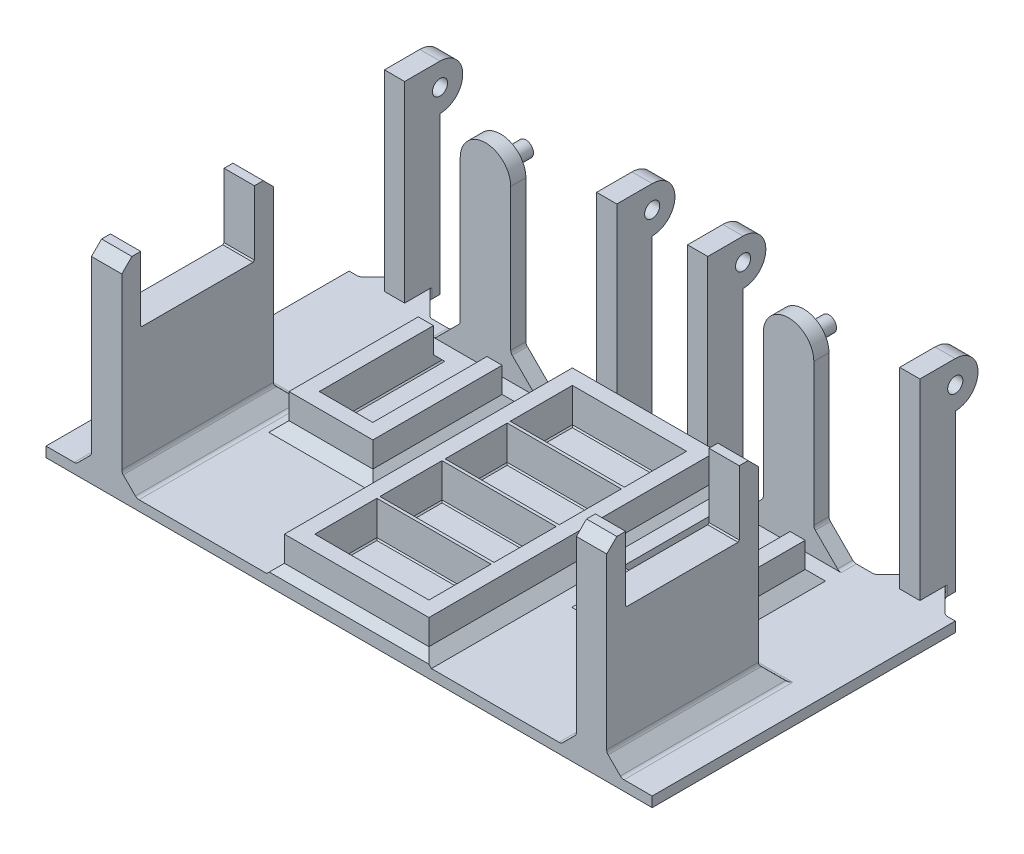
SolidWorks part; units mm, degrees
ref_plane "Front Plane" through (0, 0, 0) normal (0, 0, 1) x (1, 0, 0)
ref_plane "Top Plane" through (0, 0, 0) normal (0, 1, 0) x (1, 0, 0)
ref_plane "Right Plane" through (0, 0, 0) normal (1, 0, 0) x (0, 0, -1)
sketch "Sketch1" plane through (0, 0, 0) normal (0, 1, 0) x (1, 0, 0)
  line L0 (-60, -30) -> (-51, -30)
  line L1 (-60, -30) -> (60, -30)
  line L2 (-60, -30) -> (-60, 30)
  line L3 (-60, 30) -> (60, 30)
  line L4 (60, -30) -> (60, 30)
  line L5 (-60, -30) -> (60, 30) construction
  line L6 (-60, 30) -> (60, -30) construction
  line L7 (-51, -30) -> (-45, -30)
  line L8 (-45, -30) -> (-45, 0)
  line L9 (-45, 0) -> (-51, 0)
  line L10 (-51, 0) -> (-51, -30)
  line L11 (51, -30) -> (51, 0)
  line L12 (51, 0) -> (45, 0)
  line L13 (45, 0) -> (45, -30)
  line L14 (45, -30) -> (51, -30)
  line L15 (-38.3, 22) -> (-38.3, -3.6)
  line L16 (-38.3, -3.6) -> (-21.7, -3.6)
  line L17 (-21.7, -3.6) -> (-21.7, 22)
  line L18 (-21.7, 22) -> (-24.7, 22)
  line L19 (-24.7, 22) -> (-24.7, -0.6)
  line L20 (-24.7, -0.6) -> (-35.3, -0.6)
  line L21 (-35.3, -0.6) -> (-35.3, 22)
  line L22 (-35.3, 22) -> (-38.3, 22)
  line L23 (21.7, 22) -> (21.7, -3.6)
  line L24 (21.7, -3.6) -> (38.3, -3.6)
  line L25 (38.3, -3.6) -> (38.3, 22)
  line L26 (38.3, 22) -> (35.3, 22)
  line L27 (35.3, 22) -> (35.3, -0.6)
  line L28 (35.3, -0.6) -> (24.7, -0.6)
  line L29 (24.7, -0.6) -> (24.7, 22)
  line L30 (24.7, 22) -> (21.7, 22)
  line L31 (-25, 30) -> (-25, 27)
  line L32 (-25, 27) -> (-35, 27)
  line L33 (-35, 27) -> (-35, 30)
  line L34 (-35, 30) -> (-25, 30)
  line L35 (25, 30) -> (25, 27)
  line L36 (25, 27) -> (35, 27)
  line L37 (35, 27) -> (35, 30)
  line L38 (35, 30) -> (25, 30)
  line L39 (-53, 30) -> (-53, 37)
  line L40 (-53, 37) -> (-49, 37)
  line L41 (-49, 37) -> (-49, 30)
  line L42 (-7, 30) -> (-7, 37)
  line L43 (-7, 37) -> (-11, 37)
  line L44 (-11, 37) -> (-11, 30)
  line L45 (-11, 30) -> (-7, 30)
  line L46 (-53, 30) -> (-49, 30)
  line L47 (7, 30) -> (7, 37)
  line L48 (7, 37) -> (11, 37)
  line L49 (11, 37) -> (11, 30)
  line L50 (7, 30) -> (11, 30)
  line L51 (49, 30) -> (49, 37)
  line L52 (49, 37) -> (53, 37)
  line L53 (53, 37) -> (53, 30)
  line L54 (53, 30) -> (49, 30)
  line L55 (0, 0) -> (0, 30) construction
  line L64 (0, 0) -> (-60, 0) construction
  line L65 (-30, 0) -> (-30, 30) construction
  line L66 (0, 0) -> (60, 0) construction
  line L67 (30, 0) -> (30, 30) construction
  line L68 (-11.3, 13.2) -> (11.3, 13.2)
  line L69 (-11.3, -25.5) -> (11.3, -25.5)
  line L70 (-11.3, -25.5) -> (-11.3, 25.5)
  line L71 (-11.3, 25.5) -> (11.3, 25.5)
  line L72 (11.3, -25.5) -> (11.3, 25.5)
  line L73 (-11.3, -25.5) -> (11.3, 25.5) construction
  line L74 (-11.3, 25.5) -> (11.3, -25.5) construction
  line L75 (-14.3, -28.5) -> (14.3, -28.5)
  line L76 (-14.3, -28.5) -> (-14.3, 28.5)
  line L77 (-14.3, 28.5) -> (14.3, 28.5)
  line L78 (14.3, -28.5) -> (14.3, 28.5)
  line L79 (-14.3, -28.5) -> (14.3, 28.5) construction
  line L80 (-14.3, 28.5) -> (14.3, -28.5) construction
  line L81 (11.3, 13.2) -> (11.3, 12.6)
  line L82 (11.3, 12.6) -> (-11.3, 12.6)
  line L83 (-11.3, 12.6) -> (-11.3, 13.2)
  line L84 (-11.3, 0.3) -> (11.3, 0.3)
  line L85 (11.3, 0.3) -> (11.3, -0.3)
  line L86 (11.3, -0.3) -> (-11.3, -0.3)
  line L87 (-11.3, -0.3) -> (-11.3, 0.3)
  line L88 (-11.3, -12.6) -> (11.3, -12.6)
  line L89 (11.3, -12.6) -> (11.3, -13.2)
  line L90 (11.3, -13.2) -> (-11.3, -13.2)
  line L91 (-11.3, -13.2) -> (-11.3, -12.6)
  point P0 (0, 0)
  point P80 (36.8, 22)
  dimension "D1" = 120
  dimension "D2" = 60
  dimension "D3" = 9
  dimension "D4" = 6
  dimension "D5" = 30
  dimension "D6" = 6
  dimension "D7" = 30
  dimension "D8" = 9
  dimension "D9" = 7
  dimension "D10" = 4
  dimension "D11" = 7
  dimension "D12" = 7
  dimension "D13" = 4
  dimension "D14" = 7
  dimension "D15" = 4
  dimension "D16" = 7
  dimension "D17" = 4
  dimension "D18" = 7
  dimension "D19" = 7
  dimension "D20" = 3
  dimension "D21" = 10
  dimension "D22" = 5
  dimension "D23" = 22.6
  dimension "D24" = 10.6
  dimension "D25" = 25.6
  dimension "D26" = 3
  dimension "D27" = 3
  dimension "D28" = 3
  dimension "D29" = 25.6
  dimension "D30" = 3
  dimension "D31" = 25.6
  dimension "D32" = 3
  dimension "D33" = 3
  dimension "D34" = 10.6
  dimension "D35" = 3
  dimension "D36" = 10
  dimension "D37" = 7
  dimension "D38" = 5
  dimension "D39" = 5.3
  dimension "D40" = 5.3
  dimension "D41" = 5
  dimension "D42" = 5
  dimension "D43" = 51
  dimension "D44" = 22.6
  dimension "D45" = 3
  dimension "D46" = 3
  dimension "D47" = 0.6
  dimension "D48" = 12.3
  dimension "D49" = 0.6
  dimension "D50" = 12.3
  dimension "D51" = 12.3
  dimension "D52" = 12.3
  dimension "D53" = 25.6
extrude "Boss-Extrude1" add sketch "Sketch1" along normal blind 9 contours L29 L30 L23 L24 L25 L26 L27 L28 | L22 L15 L16 L17 L18 L19 L20 L21 region at (23.2, 0, -21.6949)
extrude "Boss-Extrude2" add sketch "Sketch1<3>" along normal blind 28 separate body contours L7 L8 L9 L10 | L12 L13 L14 L11
sketch "Sketch1<3>" plane through (0, 0, 0) normal (0, 1, 0) x (1, 0, 0) same geometry as "Sketch1"
extrude "Boss-Extrude3" add sketch "Sketch1<4>" along normal blind 40 separate body contours L40 L41 L46 L39 | L43 L44 L45 L42 | L48 L49 L50 L47 | L52 L53 L54 L51
sketch "Sketch1<4>" plane through (0, 0, 0) normal (0, 1, 0) x (1, 0, 0) same geometry as "Sketch1"
extrude "Boss-Extrude4" add sketch "Sketch1<5>" along normal blind 35.5 separate body contours L36 L37 L3 L35 | L31 L32 L33 L34 region at (30, 0, -28.5)
sketch "Sketch1<5>" plane through (0, 0, 0) normal (0, 1, 0) x (1, 0, 0) same geometry as "Sketch1"
extrude "Boss-Extrude5" add sketch "Sketch1<6>" along normal blind 2 contours L2 L3 L4 L1
sketch "Sketch1<6>" plane through (0, 0, 0) normal (0, 1, 0) x (1, 0, 0) same geometry as "Sketch1"
extrude "Boss-Extrude6" add sketch "Sketch1<8>" along normal blind 9 contours L72 L71 L70 L69 | L76 L77 L78 L75
sketch "Sketch1<8>" plane through (0, 0, 0) normal (0, 1, 0) x (1, 0, 0) same geometry as "Sketch1"
extrude "Boss-Extrude7" add sketch "Sketch1<9>" along normal blind 9 contours L68 L81 L82 L83 | L84 L85 L86 L87 | L88 L89 L90 L91
sketch "Sketch1<9>" plane through (0, 0, 0) normal (0, 1, 0) x (1, 0, 0) same geometry as "Sketch1"
sketch "Sketch2" plane through (0, 28, 0) normal (0, 1, 0) x (1, 0, 0)
  line L0 (-51, 0) -> (-45, 0)
  line L1 (-45, 0) -> (-45, -3.75)
  line L2 (-45, -30) -> (-45, 0) construction
  line L3 (-45, -3.75) -> (-51, -3.75)
  line L4 (-51, 0) -> (-51, -30) construction
  line L5 (-51, -3.75) -> (-51, 0)
  line L6 (-45, -30) -> (-45, -26.25)
  line L7 (-45, -26.25) -> (-51, -26.25)
  line L8 (-51, -26.25) -> (-51, -30)
  line L9 (-51, -30) -> (-45, -30)
  line L10 (45, 0) -> (51, 0)
  line L11 (51, 0) -> (51, -3.75)
  line L12 (51, -30) -> (51, 0) construction
  line L13 (51, -3.75) -> (45, -3.75)
  line L14 (45, 0) -> (45, -30) construction
  line L15 (45, -3.75) -> (45, 0)
  line L16 (45, -26.25) -> (51, -26.25)
  line L17 (51, -26.25) -> (51, -30)
  line L18 (51, -30) -> (45, -30)
  line L19 (45, -30) -> (45, -26.25)
  dimension "D1" = 22.5
  dimension "D2" = 3.75
  dimension "D3" = 22.5
extrude "Boss-Extrude8" add sketch "Sketch2" along normal blind 13
sketch "Sketch3" plane through (0, 0, -27) normal (0, 0, 1) x (1, 0, 0)
  line L0 (25, 35.5) -> (35, 35.5) construction
  line L1 (25, 35.5) -> (25, 2) construction
  line L2 (-25, 35.5) -> (-35, 35.5) construction
  line L3 (-35, 35.5) -> (-35, 2) construction
  line L4 (-35, 35.5) -> (-25, 35.5)
  line L5 (25, 35.5) -> (35, 35.5)
  arc A0 (35, 35.5) -> (25, 35.5) centre (30, 35.5) ccw
  arc A1 (-25, 35.5) -> (-35, 35.5) centre (-30, 35.5) ccw
  circle A2 centre (-30, 35.5) radius 1.5
  circle A3 centre (30, 35.5) radius 1.5
  line M3 (35, 35.5) -> (25, 35.5)
  dimension "D1" = 3
  dimension "D2" = 3
extrude "Boss-Extrude9" add sketch "Sketch3" against normal up to surface (3 mm away) contours A3 A0 M3 | A2 L4 A1 region at (-30, 37.769, -27) region at (30, 37.769, -27) up to face at (-30, 9.875, -30)
extrude "Boss-Extrude11" add sketch "Sketch3<5>" against normal blind 8 contours A3 | A2
sketch "Sketch3<5>" plane through (0, 0, -27) normal (0, 0, 1) x (1, 0, 0) same geometry as "Sketch3"
sketch "Sketch4" plane through (-53, 0, 0) normal (-1, 0, 0) x (0, 0, 1)
  line L2 (-30, 40) -> (-37, 40) construction
  circle A1 centre (-37, 35.5) radius 1.5
  circle A2 centre (-37, 35.5) radius 4.5
  dimension "D1" = 9
  dimension "D2" = 4.5
  dimension "D3" = 3
extrude "Boss-Extrude13" add sketch "Sketch4" against normal up to surface (4 mm away) contours A2 | A1 up to face at (-49, 16.4, -32.8)
extrude "Cut-Extrude2" cut sketch "Sketch4<4>" against normal up to surface (4 mm away) contours A1 up to face at (-49, 18.8333, -34.25)
sketch "Sketch4<4>" plane through (-53, 0, 0) normal (-1, 0, 0) x (0, 0, 1) same geometry as "Sketch4"
sketch "Sketch5" plane through (-11, 0, 0) normal (-1, 0, 0) x (0, 0, 1)
  circle A0 centre (-37, 35.5) radius 4.5
  circle A1 centre (-37, 35.5) radius 1.5
  dimension "D1" = 3
extrude "Boss-Extrude14" add sketch "Sketch5" against normal up to surface (4 mm away) up to face at (-7, 16.4, -32.8)
extrude "Cut-Extrude3" cut sketch "Sketch5<2>" against normal up to surface (4 mm away) contours A1 up to face at (-7, 18.8333, -34.25)
sketch "Sketch5<2>" plane through (-11, 0, 0) normal (-1, 0, 0) x (0, 0, 1) same geometry as "Sketch5"
sketch "Sketch7" plane through (7, 0, 0) normal (-1, 0, 0) x (0, 0, 1)
  circle A0 centre (-37, 35.5) radius 1.5
  circle A1 centre (-37, 35.5) radius 4.5
  dimension "D1" = 3
extrude "Boss-Extrude15" add sketch "Sketch7" against normal up to surface (4 mm away) up to face at (11, 16.4, -32.8)
extrude "Cut-Extrude4" cut sketch "Sketch7<2>" against normal up to surface (4 mm away) contours A0 up to face at (11, 18.8333, -34.25)
sketch "Sketch7<2>" plane through (7, 0, 0) normal (-1, 0, 0) x (0, 0, 1) same geometry as "Sketch7"
sketch "Sketch8" plane through (49, 0, 0) normal (-1, 0, 0) x (0, 0, 1)
  circle A0 centre (-37, 35.5) radius 1.5
  circle A1 centre (-37, 35.5) radius 4.5
  dimension "D1" = 3
extrude "Boss-Extrude16" add sketch "Sketch8" against normal up to surface (4 mm away) contours A0 | A1 up to face at (53, 16.4, -32.8)
extrude "Cut-Extrude5" cut sketch "Sketch8<4>" against normal up to surface (4 mm away) contours A0 up to face at (53, 18.8333, -34.25)
sketch "Sketch8<4>" plane through (49, 0, 0) normal (-1, 0, 0) x (0, 0, 1) same geometry as "Sketch8"
chamfer "Chamfer2" distance 5 angle 45 12 edges at (-49, 1, -30) (-53, 1, -30) (-25, 2, -28.5) (-35, 2, -28.5) (35, 2, -28.5) (25, 2, -28.5) (53, 1, -30) (49, 1, -30) (11, 1, -30) (7, 1, -30) (-7, 1, -30) (-11, 1, -30)
fillet "Fillet1" radius 1 24 edges at (-35, 7, -28.5) (-25, 7, -28.5) (58, 1, -30) (53, 1, -35) (49, 1, -35) (44, 1, -30) (25, 7, -28.5) (40, 2, -28.5) (35, 7, -28.5) (20, 2, -28.5) (16, 1, -30) (11, 1, -35) (7, 1, -35) (2, 1, -30) (-2, 1, -30) (-7, 1, -35) (-11, 1, -35) (-16, 1, -30) (-20, 2, -28.5) (-40, 2, -28.5) (-44, 1, -30) (-49, 1, -35) (-58, 1, -30) (-53, 1, -35)
chamfer "Chamfer3" distance 3 angle 45 6 edges at (45, 2, 15) (48, 2, 0) (51, 2, 15) (-45, 2, 15) (-48, 2, 0) (-51, 2, 15)
fillet "Fillet2" radius 1 12 edges at (-42, 2, 13.5) (-45, 5, 15) (-48, 2, -3) (-48, 5, 0) (-51, 5, 15) (-54, 2, 13.5) (51, 5, 15) (42, 2, 13.5) (45, 5, 15) (48, 5, 0) (48, 2, -3) (54, 2, 13.5)
chamfer "Chamfer4" distance 0.25 angle 45 26 edges at (0, 2, -13.2) (-11.3, 2, -19.35) (0, 2, -25.5) (11.3, 2, -19.35) (0, 2, -12.6) (-11.3, 2, -6.45) (0, 2, -0.3) (11.3, 2, -6.45) (0, 2, 0.3) (-11.3, 2, 6.45) (0, 2, 12.6) (11.3, 2, 6.45) (11.3, 2, 19.35) (0, 2, 13.2) (-11.3, 2, 19.35) (0, 2, 25.5) (-24.7, 2, -10.7) (-35.3, 2, -10.7) (-30, 2, 0.6) (35.3, 2, -10.7) (30, 2, 0.6) (24.7, 2, -10.7) (-48, 28, 26.25) (-48, 28, 3.75) (48, 28, 3.75) (48, 28, 26.25)
chamfer "Chamfer5" distance 2 angle 45 18 edges at (-23.325, 2, -22) (-21.7, 2, -9.2) (-30, 2, 3.6) (-36.675, 2, -22) (-38.3, 2, -9.2) (23.325, 2, -22) (21.7, 2, -9.2) (30, 2, 3.6) (36.675, 2, -22) (38.3, 2, -9.2) (0, 2, -28.5) (-14.3, 2, 0) (0, 2, 28.5) (14.3, 2, 0) (-48, 41, 0) (-48, 41, 30) (48, 41, 0) (48, 41, 30)
